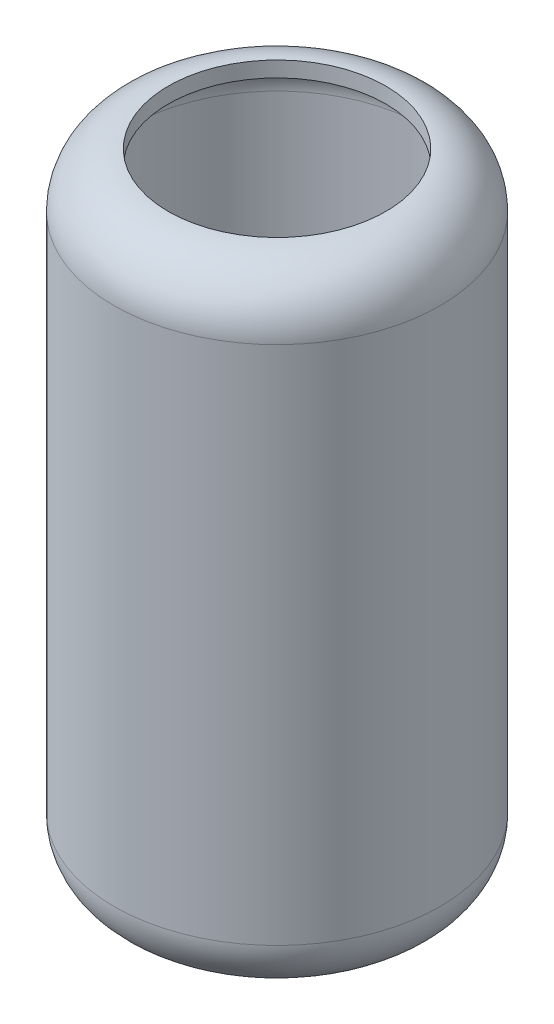
SolidWorks part; units mm, degrees
ref_plane "Front Plane" through (0, 0, 0) normal (0, 0, 1) x (1, 0, 0)
ref_plane "Top Plane" through (0, 0, 0) normal (0, 1, 0) x (1, 0, 0)
ref_plane "Right Plane" through (0, 0, 0) normal (1, 0, 0) x (0, 0, -1)
sketch "Sketch1" plane through (0, 0, 0) normal (0, 1, 0) x (1, 0, 0)
  circle A0 centre (0, 0) radius 10.5
extrude "Boss-Extrude1" add sketch "Sketch1" along normal blind 40.5
fillet "Fillet1" radius 3.5 2 edges at (0, 0, 10.5) (0, 40.5, 10.5)
sketch "Sketch2" plane through (0, 0, 0) normal (1, 0, 0) x (0, 0, -1)
  line L1 (-17.8369, 48.8479) -> (23.4385, 48.8479)
  line L2 (-17.8369, 48.8479) -> (-17.8369, -1.7144)
  line L3 (-17.8369, -1.7144) -> (23.4385, -1.7144)
  line L4 (23.4385, 48.8479) -> (23.4385, -1.7144)
extrude "Cut-Extrude1" [suppressed] cut sketch "Sketch2" against normal blind 40.5
shell "Shell3" [suppressed] thickness 1
shell "Shell4" thickness 1 removed face at (0, 40.5, 7)
